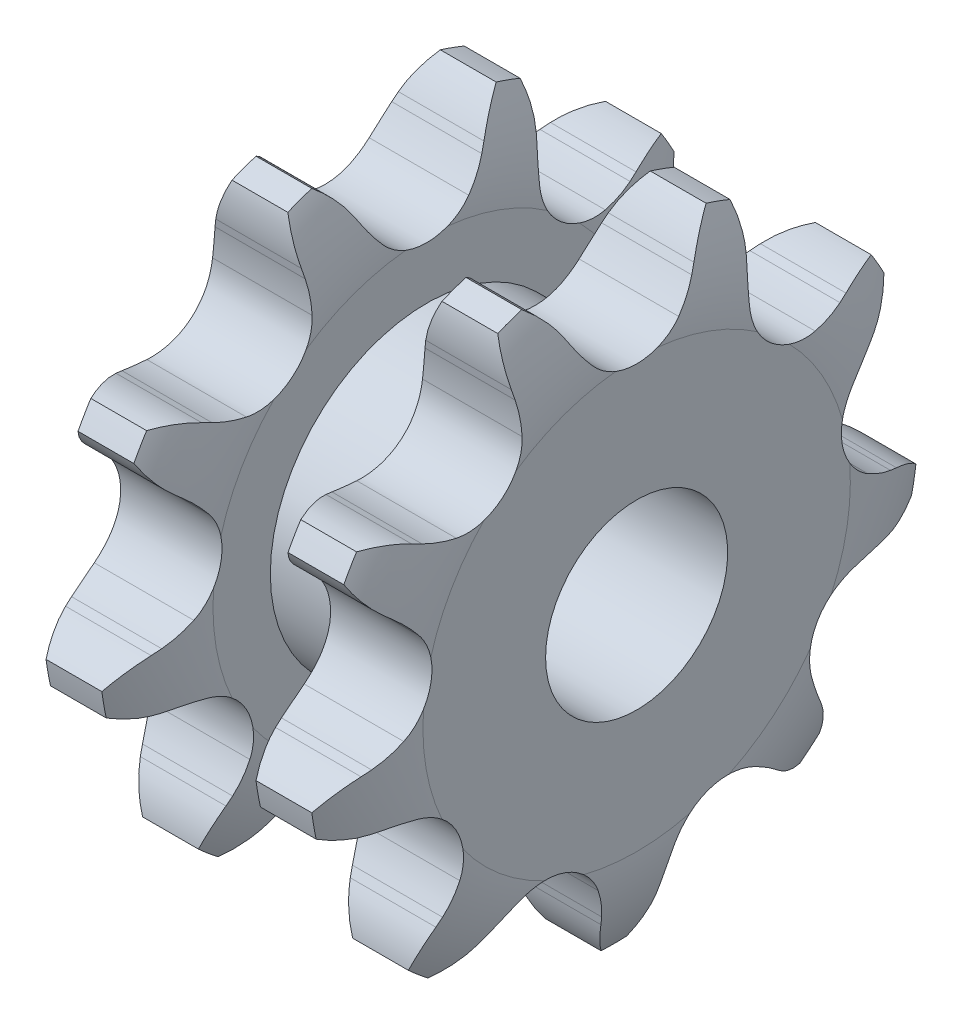
SolidWorks part; units mm, degrees
ref_plane "Plane1" through (0, 0, 0) normal (0, 0, 1) x (1, 0, 0)
ref_plane "Plane2" through (0, 0, 0) normal (0, 1, 0) x (1, 0, 0)
ref_plane "Plane3" through (0, 0, 0) normal (1, 0, 0) x (0, 0, -1)
sketch "Clipboard" plane through (0, 0, 0) normal (0, 1, 0) x (1, 0, 0)
  line L0 (0, 0) -> (25.0873, -3.9734)
  line L1 (-15, 0) -> (100, 0) construction
  line L2 (0, 0) -> (-2.1039, 2.3779)
  line L3 (0, 0) -> (-11.863, 4.5341)
  line L4 (0, 0) -> (15.6796, 2.4834)
  line L5 (0, 0) -> (-47.5972, -17.7524)
  line L6 (0, 0) -> (-35.9946, -24.2857)
  line L7 (-2.1039, 2.3779) -> (47.7628, 12.071)
  line L8 (-76.2, 38.1) -> (-47.9044, 38.1)
  line L9 (-73.2054, 38.5461) -> (-73.0531, 38.5485)
  line L10 (-73.0533, 76.1892) -> (-43.7671, 76.1892)
  circle A0 centre (0, 0) radius 7.9375
  circle A1 centre (0, 0) radius 21.812
  circle A2 centre (0, 0) radius 25.4
  dimension "Num_teeth" = 9
  dimension "Thickness" = 43.4213
sketch "BasProSke" plane through (0, 0, 0) normal (0, 1, 0) x (1, 0, 0)
  line L0 (-10, 0) -> (60, 0) construction
  line L1 (0, 0) -> (0, 29.813)
  line L2 (0, 0) -> (43.4213, 0)
  line L3 (43.4213, 0) -> (43.4213, 29.813)
  line L4 (40.2463, 42.513) -> (3.175, 42.513)
  arc A0 (0, 29.813) -> (3.175, 42.513) centre (26.9875, 29.813) cw
  arc A1 (43.4213, 29.813) -> (40.2463, 42.513) centre (16.4338, 29.813) ccw
  dimension "D1" = 26.9875
  dimension "Thickness" = 43.4213
  dimension "Diameter" = 85.0259
  dimension "H1" = 12.7
  dimension "G1" = 3.175
revolve "Base-Revolve" add sketch "BasProSke" angle 360 about L0
sketch "GrvSke" plane through (0, 0, 0) normal (0, 1, 0) x (1, 0, 0)
  line L0 (14.1351, 29.813) -> (14.1351, 21.812)
  line L1 (14.1351, 21.812) -> (29.2862, 21.812)
  line L2 (29.2862, 21.812) -> (29.2862, 29.813)
  line L3 (10.9601, 42.513) -> (32.4612, 42.513)
  line L4 (21.7106, 0) -> (21.7106, 52.07) construction
  line L5 (-10, 0) -> (60, 0) construction
  line L6 (0, 0) -> (35.56, 0) construction
  arc A0 (29.2862, 29.813) -> (32.4612, 42.513) centre (56.2737, 29.813) cw
  arc A1 (14.1351, 29.813) -> (10.9601, 42.513) centre (-12.8524, 29.813) ccw
  dimension "Diameter" = 85.0259
  dimension "H1" = 12.7
  dimension "G1" = 3.175
revolve "Groove" cut sketch "GrvSke" angle 360 about L6
pattern_linear "Grooves" [suppressed]
sketch "TooCutSke" plane through (0, 0, 0) normal (1, 0, 0) x (0, 0, -1)
  line L0 (8.4728, 35.2524) -> (9.083, 36.3141)
  line L1 (0, 0) -> (0, 107) construction
  line L2 (0, 37.1323) -> (-10, 37.1323) construction
  line L3 (-8.4728, 35.2524) -> (-9.083, 36.3141)
  arc A0 (5.9876, 31.8038) -> (8.4728, 35.2524) centre (-9.4872, 45.5752) ccw
  arc A1 (5.9876, 31.8038) -> (-5.9876, 31.8038) centre (0, 37.1323) cw
  arc A2 (9.083, 36.3141) -> (20.8847, 43.143) centre (20.8847, 29.5309) cw
  arc A3 (-5.9876, 31.8038) -> (-8.4728, 35.2524) centre (9.4872, 45.5752) cw
  arc A4 (-9.083, 36.3141) -> (-20.8847, 43.143) centre (-20.8847, 29.5309) ccw
  arc A5 (20.8847, 43.143) -> (-20.8847, 43.143) centre (0, 0) ccw
  dimension "Pitch_radius" = 37.1323
  dimension "V" = 7.6014
extrude "ToothCut" cut sketch "TooCutSke" along normal through all
pattern_circular "TeethCuts" count 9 every 40 about axis through (-10, 0, 0) along (1, 0, 0) of "ToothCut"
sketch "HubNeaOneSke" plane through (0, 0, 0) normal (-1, 0, 0) x (0, 0, 1)
  circle A0 centre (0, 0) radius 21.812
  dimension "Diameter" = 43.6239
extrude "HubNearOne" [suppressed] add sketch "HubNeaOneSke" along normal blind 7.3788
sketch "HubNeaBotSke" plane through (0, 0, 0) normal (-1, 0, 0) x (0, 0, 1)
  circle A0 centre (0, 0) radius 21.812
  dimension "Diameter" = 43.6239
extrude "HubNearBoth" [suppressed] add sketch "HubNeaBotSke" along normal blind 3.6894
ref_plane "FarPln" through (43.4213, 0, 0) normal (1, 0, 0) x (0, 0, -1)
sketch "HubFarSke" plane through (43.4213, 0, 0) normal (1, 0, 0) x (0, 0, -1)
  circle A0 centre (0, 0) radius 21.812
  dimension "Diameter" = 43.6239
extrude "HubFar" [suppressed] add sketch "HubFarSke" along normal blind 3.6894
sketch "BorSke" plane through (0, 0, 0) normal (1, 0, 0) x (0, 0, -1)
  circle A0 centre (0, 0) radius 12.7
  dimension "Diameter" = 25.4
extrude "Bore" cut sketch "BorSke" along normal mid plane 101.6001
sketch "KeySke" plane through (0, 0, 0) normal (1, 0, 0) x (0, 0, -1)
  line L0 (-3.175, 0) -> (-3.175, 15.5956)
  line L1 (-3.175, 15.5956) -> (3.175, 15.5956)
  line L2 (3.175, 15.5956) -> (3.175, 0)
  line L3 (0, 0) -> (0, 34) construction
  line L4 (-3.175, 0) -> (3.175, 0)
  dimension "Offset" = 15.5956
  dimension "Width" = 6.35
extrude "Keyway" [suppressed] cut sketch "KeySke" along normal mid plane 101.6001
pattern_circular "Keyway2" [suppressed] count 2 every 90 about axis through (-10, 0, 0) along (1, 0, 0)
equation "\"Num_teeth@Clipboard\" = int( \"Num_teeth@Clipboard\" )"
equation "\"Num_teeth@Clipboard\" = ((sgn( \"Num_teeth@Clipboard\" - 5.0)+1)*( \"Num_teeth@Clipboard\" - 5.0))/2 +5.0"
equation "\"Num_teeth@Clipboard\" = ((sgn( \"Num_teeth@Clipboard\" - 200.0)-1)*( \"Num_teeth@Clipboard\" - 200.0))/-2 +200.0"
equation "\"MHD@Clipboard\" = \"Pitch@Clipboard\" * (1.0 / tan(3.14159265 / \"Num_teeth@Clipboard\" ) - 1.0) - 0.03"
equation "\"Thickness@Clipboard\"  = \"Width@Clipboard\" * \"Width_factor@Clipboard\" - \"Width_const@Clipboard\" + (\"Num_strands@Clipboard\" - 1) * \"Transv_pitch@Clipboard\""
equation "\"OAL@Clipboard\" = \"Thickness@Clipboard\""
equation "\"MHD@Clipboard\" = ((sgn( \"MHD@Clipboard\" - \"Hub_dia@Clipboard\" )-1)*( \"MHD@Clipboard\" - \"Hub_dia@Clipboard\" ))/-2+ \"Hub_dia@Clipboard\""
equation "\"OAL@Clipboard\" = ((sgn( \"OAL@Clipboard\" - \"Overall_len@Clipboard\" )+1)*( \"OAL@Clipboard\" - \"Overall_len@Clipboard\" ))/2 + \"Overall_len@Clipboard\" + 0.000002"
equation "\"Num_teeth@TeethCuts\" = int( \"Show_teeth@Clipboard\" ) + 1"
equation "\"Num_teeth@TeethCuts\" = ((sgn( \"Num_teeth@TeethCuts\" - \"Num_teeth@Clipboard\" )-1)*( \"Num_teeth@TeethCuts\" - \"Num_teeth@Clipboard\" ))/-2+ \"Num_teeth@Clipboard\""
equation "\"Num_teeth@TeethCuts\" = ((sgn( \"Num_teeth@TeethCuts\" - 2.0)+1)*( \"Num_teeth@TeethCuts\" - 2.0))/2 +2.0"
equation "\"Angle@TeethCuts\" = 360.0 / \"Num_teeth@Clipboard\""
equation "\"Pitch_radius@TooCutSke\" = ( \"Pitch@Clipboard\" / 2.0) / sin(3.14159265 / \"Num_teeth@Clipboard\" )  'ma"
equation "\"R@TooCutSke\"  = \"Dr@Clipboard\" * 0.5025 + 0.0015"
equation "\"A@TooCutSke\" = 35.0 + (60.0 / \"Num_teeth@Clipboard\")"
equation "\"E@TooCutSke\"  = \"Dr@Clipboard\" * 1.3025 + 0.0015"
equation "\"B@TooCutSke\"  = 18.0 - (56.0 / \"Num_teeth@Clipboard\" )"
equation "\"W@TooCutSke\" = 1.4 * \"Dr@Clipboard\" * cos(3.14159265 / \"Num_teeth@Clipboard\" )"
equation "\"V@TooCutSke\" = 1.4 * \"Dr@Clipboard\" * sin(3.14159265 / \"Num_teeth@Clipboard\" )"
equation "\"Diameter@BasProSke\" = 2.0 * ( (0.3 * \"Pitch@Clipboard\" ) +  \"Pitch@Clipboard\" / 2.0 / tan(3.14159265 / \"Num_teeth@Clipboard\" ))"
equation "\"Thickness@BasProSke\"  = \"Thickness@Clipboard\""
equation "\"G1@BasProSke\" =  \"Chamfer_wid@Clipboard\""
equation "\"G2@BasProSke\" =  \"Chamfer_wid@Clipboard\""
equation "\"H1@BasProSke\" =  \"Chamfer_dep@Clipboard\""
equation "\"H2@BasProSke\" =  \"Chamfer_dep@Clipboard\""
equation "\"Diameter@GrvSke\" = \"Diameter@BasProSke\""
equation "\"G1@GrvSke\" = \"Chamfer_wid@Clipboard\""
equation "\"H1@GrvSke\" = \"Chamfer_dep@Clipboard\""
equation "\"Grv_diam@GrvSke\" =  \"Pitch@Clipboard\" * (1.0 / tan(3.14159265 / \"Num_teeth@Clipboard\" ) - 1.0) - 0.03"
equation "\"Grv_width@GrvSke\" =  \"Transv_pitch@Clipboard\" - ( \"Width@Clipboard\" * \"Width_factor@Clipboard\" - \"Width_const@Clipboard\" )"
equation "\"Offset@GrvSke\" = \"Grv_width@GrvSke\" / 2.0 + ( \"Width@Clipboard\" * \"Width_factor@Clipboard\" - \"Width_const@Clipboard\" )"
equation "\"Offset@Grooves\" = \"Transv_pitch@Clipboard\""
equation "\"Num_grvs@Grooves\" = \"Num_strands@Clipboard\""
equation "\"Num_grvs@Grooves\" = \"Num_grvs@Grooves\" - 1 * sgn( \"Num_grvs@Grooves\" -1)"
equation "\"Diameter@HubNeaOneSke\" = \"MHD@Clipboard\""
equation "\"Length@HubNearOne\" = \"OAL@Clipboard\" - \"Thickness@BasProSke\""
equation "\"Diameter@HubNeaBotSke\" = \"MHD@Clipboard\""
equation "\"Length@HubNearBoth\" = ( \"OAL@Clipboard\" - \"Thickness@BasProSke\" ) / 2.0"
equation "\"Thickness@FarPln\" = \"Thickness@BasProSke\""
equation "\"Diameter@HubFarSke\" = \"MHD@Clipboard\""
equation "\"Length@HubFar\" = ( \"OAL@Clipboard\" - \"Thickness@BasProSke\" ) / 2.0"
equation "\"D1@Bore\" = \"OAL@Clipboard\" * 2.0"
equation "\"D1@Keyway\" = \"OAL@Clipboard\" * 2.0"
equation "\"Offset@KeySke\" = \"T_dim@Clipboard\" - \"Diameter@BorSke\" / 2.0"
